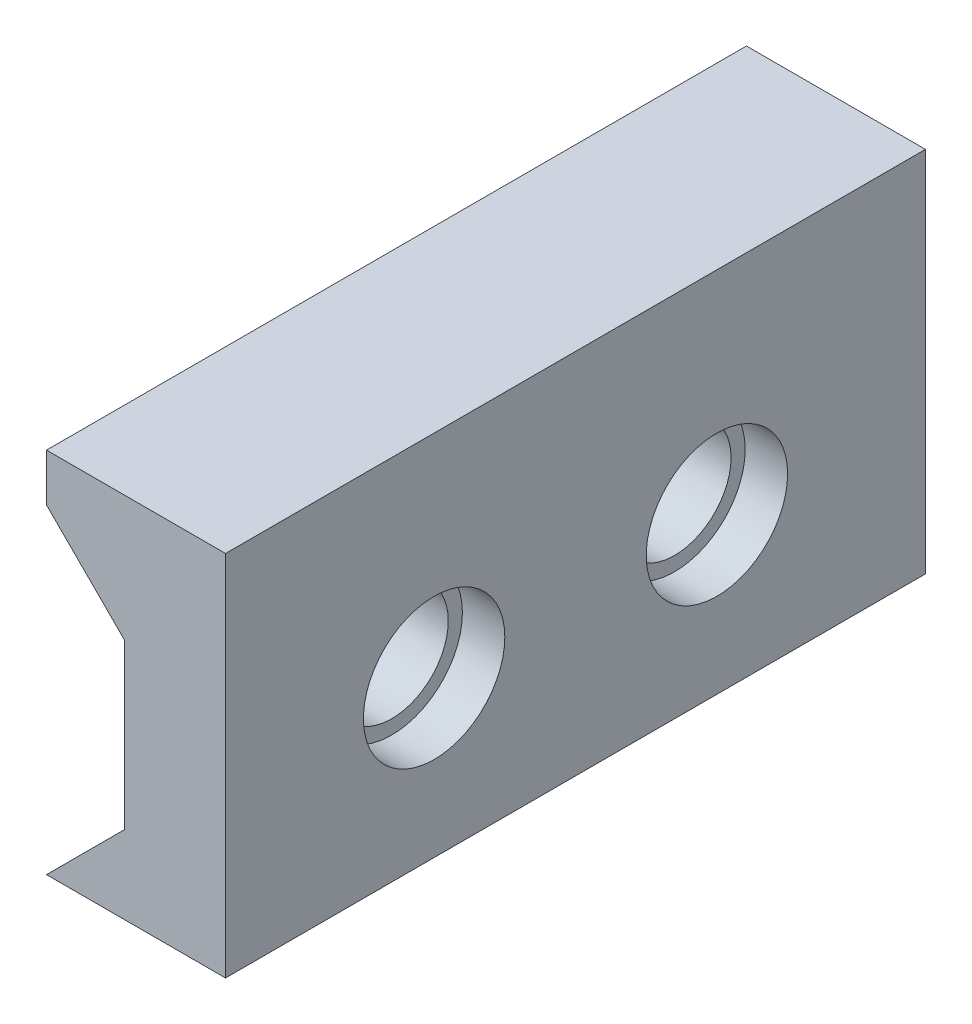
SolidWorks part; units mm, degrees
ref_plane "Płaszczyzna przednia" through (0, 0, 0) normal (0, 0, 1) x (1, 0, 0)
ref_plane "Płaszczyzna górna" through (0, 0, 0) normal (0, 1, 0) x (1, 0, 0)
ref_plane "Płaszczyzna prawa" through (0, 0, 0) normal (1, 0, 0) x (0, 0, -1)
sketch "Szkic1" plane through (0, 0, 0) normal (0, 0, 1) x (1, 0, 0)
  line L0 (14, -7.5) -> (7.67, -7.5)
  line L4 (14, -7.5) -> (14, 5.5)
  line L5 (-14, -5.5) -> (14, 5.5) construction
  line L6 (-12.5178, 6.7059) -> (14, -7.5) construction
  line L7 (7.67, -7.5) -> (10.435, -4.735)
  line L8 (10.435, -4.735) -> (10.435, 1.055)
  line L9 (10.435, 1.055) -> (7.67, 3.82)
  line L10 (7.67, 3.82) -> (7.67, 5.5)
  line L11 (7.67, 5.5) -> (14, 5.5)
  point P0 (0, 0)
  dimension "D1" = 13
extrude "Dodanie-wyciągnięcie1" add sketch "Szkic1" along normal blind 24.75
sketch "Szkic2" plane through (14, 0, 0) normal (1, 0, 0) x (0, 0, -1)
  line L0 (-24.75, -7.5) -> (0, -7.5) construction
  line L1 (-24.75, 5.5) -> (0, 5.5) construction
  circle A0 centre (-17.375, -2) radius 2
  circle A1 centre (-7.375, -2) radius 2
  point P3 (0, 0)
  point P4 (0, 0)
  point P6 (-6.9212, 5.5)
  dimension "D1" = 13
  dimension "D2" = 5.5
  dimension "D3" = 5.5
extrude "Wytnij-wyciągnięcie1" cut sketch "Szkic2" against normal blind 14
sketch "Szkic3" plane through (14, 0, 0) normal (1, 0, 0) x (0, 0, -1)
  circle A0 centre (-17.375, -2) radius 2.5
  circle A1 centre (-7.375, -2) radius 2.5
extrude "Wytnij-wyciągnięcie2" cut sketch "Szkic3" against normal blind 1.5
